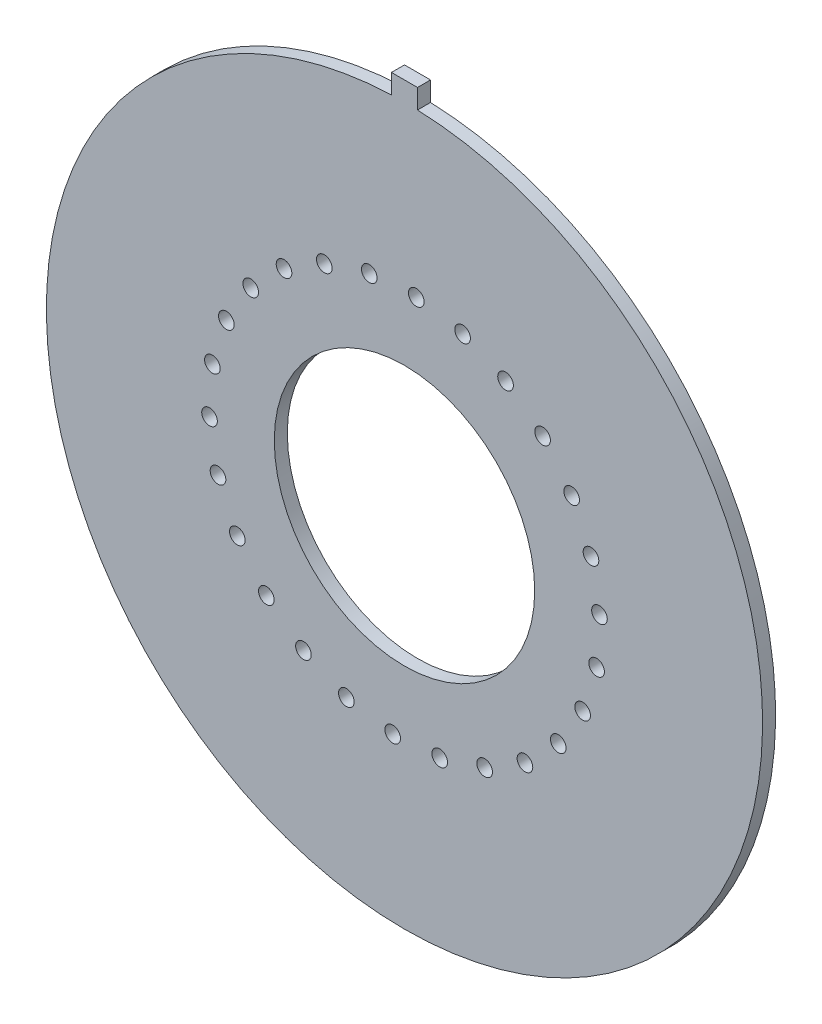
SolidWorks part; units mm, degrees
ref_plane "Front Plane" through (0, 0, 0) normal (0, 0, 1) x (1, 0, 0)
ref_plane "Top Plane" through (0, 0, 0) normal (0, 1, 0) x (1, 0, 0)
ref_plane "Right Plane" through (0, 0, 0) normal (1, 0, 0) x (0, 0, -1)
sketch "PCB dimension" plane through (0, 0, 0) normal (0, 0, 1) x (1, 0, 0)
  line L0 (0, 0) -> (0, 42.7396) construction
  line L1 (-1, 27.4818) -> (-1, 28.9818)
  line L2 (-1, 28.9818) -> (1, 28.9818)
  line L3 (1, 28.9818) -> (1, 27.4818)
  line L4 (0, 0) -> (40.2767, 0) construction
  line L5 (0, 0) -> (37.4859, 2.2675) construction
  arc A0 (-1, 27.4818) -> (1, 27.4818) centre (0, 0) ccw
  circle A1 centre (14.9726, 0.9057) radius 0.6
  circle A2 centre (14.7543, -2.7038) radius 0.6
  circle A3 centre (13.6785, -6.1562) radius 0.6
  circle A4 centre (11.8078, -9.2508) radius 0.6
  circle A5 centre (9.2508, -11.8078) radius 0.6
  circle A6 centre (6.1562, -13.6785) radius 0.6
  circle A7 centre (2.7038, -14.7543) radius 0.6
  circle A8 centre (-0.9057, -14.9726) radius 0.6
  circle A9 centre (-4.4625, -14.3208) radius 0.6
  circle A10 centre (-7.7601, -12.8367) radius 0.6
  circle A11 centre (-10.6066, -10.6066) radius 0.6
  circle A12 centre (-12.8367, -7.7601) radius 0.6
  circle A13 centre (-14.3208, -4.4625) radius 0.6
  circle A14 centre (-14.9726, -0.9057) radius 0.6
  circle A15 centre (-14.7543, 2.7038) radius 0.6
  circle A16 centre (-13.6785, 6.1562) radius 0.6
  circle A17 centre (-11.8078, 9.2508) radius 0.6
  circle A18 centre (-9.2508, 11.8078) radius 0.6
  circle A19 centre (-6.1562, 13.6785) radius 0.6
  circle A20 centre (-2.7038, 14.7543) radius 0.6
  circle A21 centre (0.9057, 14.9726) radius 0.6
  circle A22 centre (4.4625, 14.3208) radius 0.6
  circle A23 centre (7.7601, 12.8367) radius 0.6
  circle A24 centre (10.6066, 10.6066) radius 0.6
  circle A25 centre (12.8367, 7.7601) radius 0.6
  circle A26 centre (14.3208, 4.4625) radius 0.6
  circle A27 centre (0, 0) radius 10
  point P6 (0, 28.9818)
  point P64 (0, 0)
  dimension "D1" = 55
  dimension "D5" = 1.2
  dimension "D8" = 20
  dimension "D2" = 1.5
  dimension "D3" = 2
  dimension "D4" = 3.462
  dimension "D6" = 15
  dimension "D7" = 26
extrude "Boss-Extrude1" add sketch "PCB dimension" along normal blind 1
equation "\"D4@PCB dimension\"=360/26/4"
